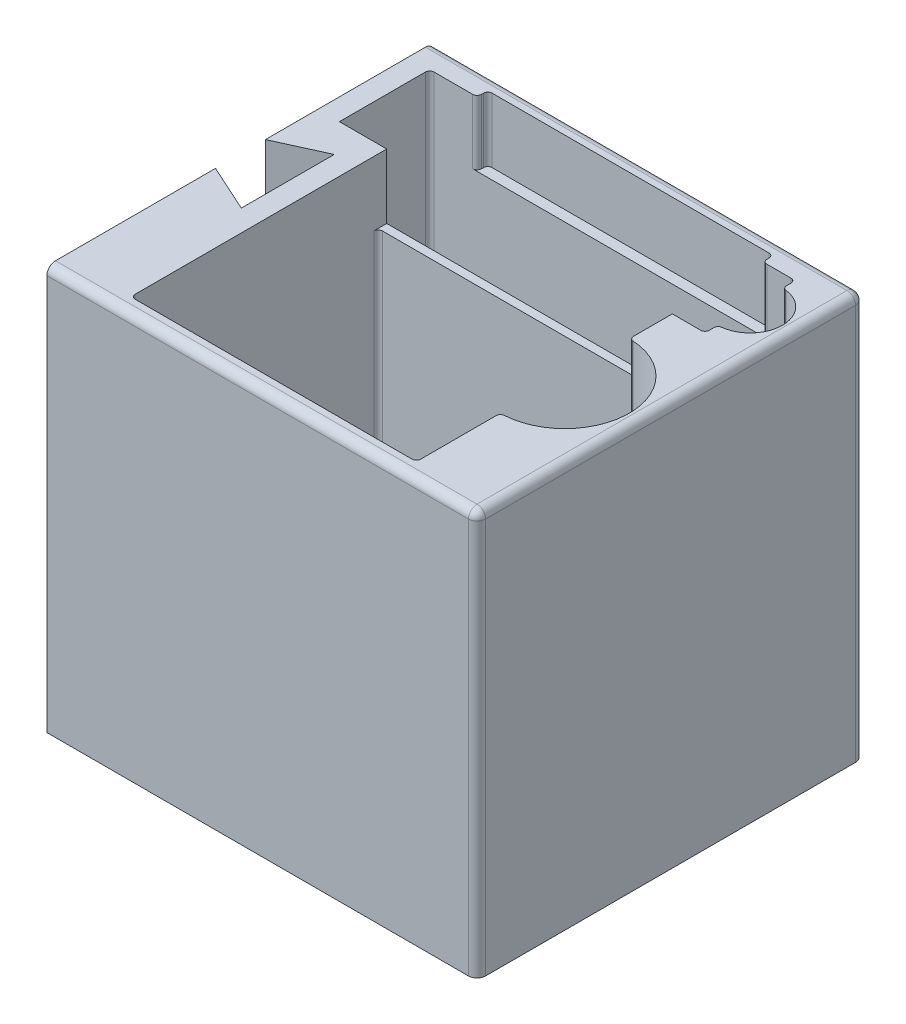
SolidWorks part; units mm, degrees
note: The reader was unsure of these and kept them because the rebuilt part matched: shared geometry of "Sketch6<2>".
ref_plane "Front Plane" through (0, 0, 0) normal (0, 0, 1) x (1, 0, 0)
ref_plane "Top Plane" through (0, 0, 0) normal (0, 1, 0) x (1, 0, 0)
ref_plane "Right Plane" through (0, 0, 0) normal (1, 0, 0) x (0, 0, -1)
sketch "Sketch1" plane through (0, 0, 0) normal (0, 1, 0) x (1, 0, 0)
  line L0 (0, 64.516) -> (13.97, 70.866)
  line L1 (0, 0) -> (127, 0)
  line L2 (0, 0) -> (0, 49.784)
  line L3 (0, 114.3) -> (127, 114.3)
  line L4 (127, 0) -> (127, 114.3)
  line L5 (13.97, 70.866) -> (13.97, 43.434)
  line L6 (13.97, 43.434) -> (0, 49.784)
  line L7 (0, 64.516) -> (0, 114.3)
  dimension "D1" = 127
  dimension "D2" = 114.3
  dimension "D3" = 13.97
  dimension "D4" = 43.434
  dimension "D5" = 43.434
  dimension "D6" = 49.784
  dimension "D7" = 49.784
extrude "Boss-Extrude1" add sketch "Sketch1" along normal blind 119.38
sketch "Sketch2" plane through (0, 119.38, 0) normal (0, 1, 0) x (1, 0, 0)
  line L0 (0, 0) -> (127, 0) construction
  line L1 (20.32, 77.47) -> (104.648, 77.47)
  line L2 (20.32, 77.47) -> (20.32, 19.05)
  line L3 (20.32, 19.05) -> (104.648, 19.05)
  line L4 (104.648, 77.47) -> (104.648, 67.31)
  line L5 (104.648, 29.21) -> (104.648, 19.05)
  line L6 (13.97, 70.866) -> (13.97, 43.434) construction
  arc A0 (104.648, 67.31) -> (104.648, 29.21) centre (104.648, 48.26) cw
  point P12 (20.32, 48.26)
  dimension "D5" = 19.05
  dimension "D6" = 38.1
  dimension "D1" = 84.328
  dimension "D2" = 58.42
  dimension "D3" = 19.05
  dimension "D4" = 6.35
  dimension "D7" = 19.05
extrude "Cut-Extrude1" cut sketch "Sketch2" against normal blind 115.57
sketch "Sketch5" plane through (0, 119.38, 0) normal (0, 1, 0) x (1, 0, 0)
  line L0 (0, 0) -> (127, 0) construction
  line L1 (20.32, 4.445) -> (104.648, 4.445)
  line L2 (20.32, 4.445) -> (20.32, 109.855)
  line L3 (20.32, 109.855) -> (104.648, 109.855)
  line L4 (104.648, 4.445) -> (104.648, 109.855)
  line L7 (13.97, 70.866) -> (13.97, 43.434) construction
  dimension "D1" = 4.445
  dimension "D2" = 84.328
  dimension "D3" = 105.41
  dimension "D4" = 6.35
extrude "Cut-Extrude4" cut sketch "Sketch5" against normal blind 19.05
sketch "Sketch6" plane through (0, 100.33, 0) normal (0, 1, 0) x (1, 0, 0)
  line L0 (20.32, 109.855) -> (20.32, 77.47) construction
  line L1 (6.35, 106.68) -> (114.3, 106.68)
  line L2 (6.35, 106.68) -> (6.35, 80.01)
  line L3 (6.35, 80.01) -> (114.3, 80.01)
  line L4 (114.3, 106.68) -> (114.3, 102.87)
  line L5 (127, 114.3) -> (0, 114.3) construction
  line L6 (114.3, 83.8238) -> (114.3, 80.01)
  arc A0 (114.3, 102.87) -> (114.3, 83.8238) centre (114.3, 93.3469) cw
  dimension "D6" = 9.5231
  dimension "D1" = 13.97
  dimension "D2" = 107.95
  dimension "D3" = 7.62
  dimension "D4" = 26.67
  dimension "D5" = 3.8138
  dimension ".15" = 3.81
extrude "Cut-Extrude5" cut sketch "Sketch6" against normal blind 24.13 and the other way up to next
extrude "Cut-Extrude6" cut sketch "Sketch6<2>" against normal blind 43.18
sketch "Sketch6<2>" plane through (0, 100.33, 0) normal (0, 1, 0) x (1, 0, 0) same geometry as "Sketch6"
fillet "Fillet2" radius 2.54 5 edges at (63.5, 119.38, 0) (63.5, 119.38, -114.3) (127, 119.38, -57.15) (127, 59.69, -114.3) (127, 59.69, 0)
fillet "Fillet3" radius 1.27 16 edges at (20.32, 52.07, -19.05) (20.32, 52.07, -77.47) (104.648, 61.595, -67.31) (104.648, 61.595, -29.21) (104.648, 52.07, -19.05) (20.32, 109.855, -4.445) (104.648, 109.855, -109.855) (20.32, 109.855, -109.855) (104.648, 109.855, -4.445) (104.648, 109.855, -106.68) (6.35, 88.265, -106.68) (20.32, 109.855, -106.68) (114.3, 88.265, -106.68) (114.3, 88.265, -102.87) (114.3, 88.265, -83.8238) (114.3, 88.265, -80.01)
